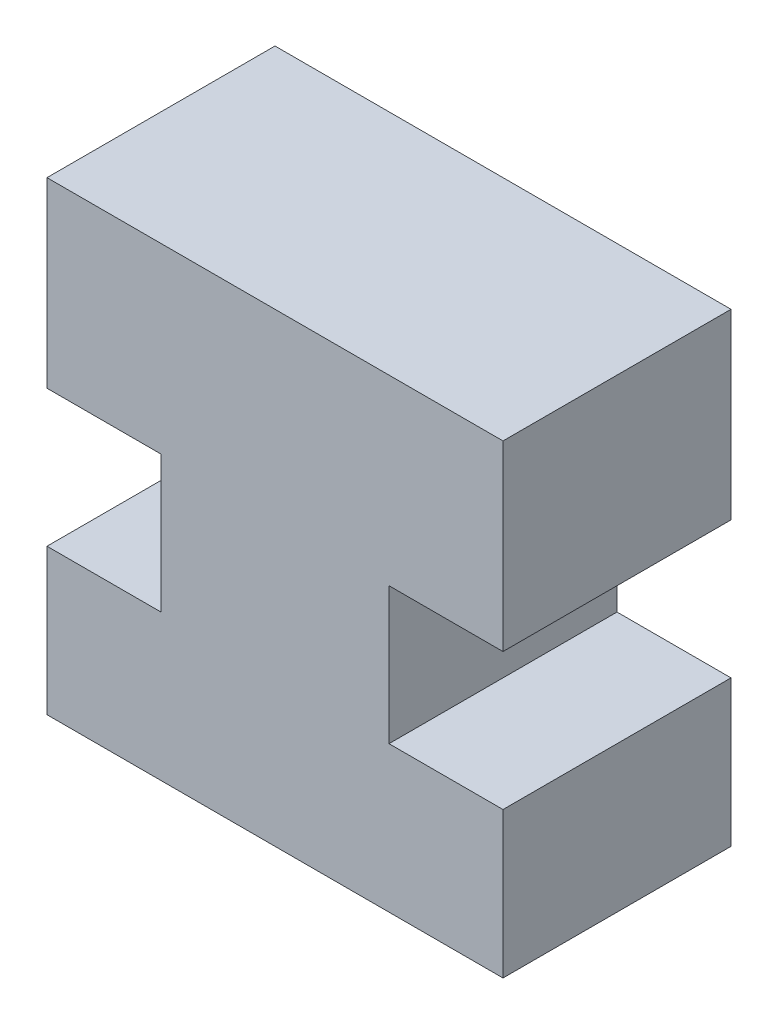
SolidWorks part; units mm, degrees
ref_plane "Front Plane" through (0, 0, 0) normal (0, 0, 1) x (1, 0, 0)
ref_plane "Top Plane" through (0, 0, 0) normal (0, 1, 0) x (1, 0, 0)
ref_plane "Right Plane" through (0, 0, 0) normal (1, 0, 0) x (0, 0, -1)
sketch "Sketch2" plane through (0, 0, 0) normal (0, 0, 1) x (1, 0, 0)
  line L0 (0, 0) -> (12.7, 0)
  line L1 (12.7, 0) -> (12.7, -5.08)
  line L2 (12.7, -5.08) -> (9.525, -5.08)
  line L3 (9.525, -5.08) -> (9.525, -8.89)
  line L4 (9.525, -8.89) -> (12.7, -8.89)
  line L5 (12.7, -8.89) -> (12.7, -12.954)
  line L6 (12.7, -12.954) -> (0, -12.954)
  line L7 (0, -12.954) -> (0, -8.89)
  line L8 (0, -8.89) -> (3.175, -8.89)
  line L9 (3.175, -8.89) -> (3.175, -5.08)
  line L10 (3.175, -5.08) -> (0, -5.08)
  line L11 (0, -5.08) -> (0, 0)
  dimension "D1" = 12.7
  dimension "D2" = 12.7
  dimension "D3" = 5.08
  dimension "D4" = 3.81
  dimension "D5" = 5.08
  dimension "D6" = 3.81
  dimension "D7" = 7.874
  dimension "D8" = 3.175
  dimension "D9" = 3.175
extrude "body" add sketch "Sketch2" along normal blind 6.35
